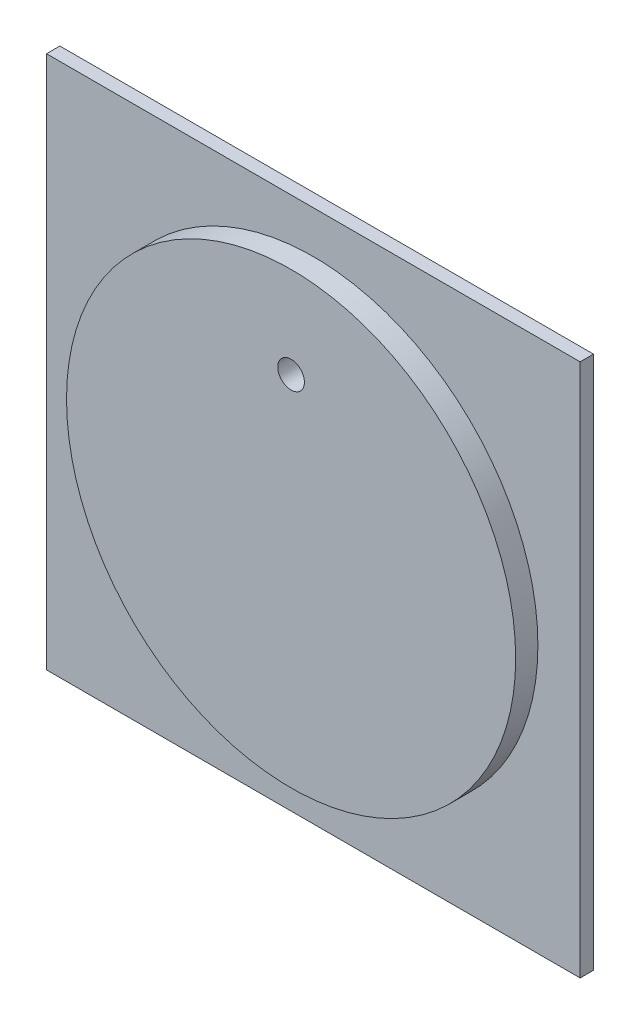
SolidWorks part; units mm, degrees
ref_plane "Front Plane" through (0, 0, 0) normal (0, 0, 1) x (1, 0, 0)
ref_plane "Top Plane" through (0, 0, 0) normal (0, 1, 0) x (1, 0, 0)
ref_plane "Right Plane" through (0, 0, 0) normal (1, 0, 0) x (0, 0, -1)
sketch "Sketch1" plane through (0, 0, 0) normal (0, 0, 1) x (1, 0, 0)
  line L1 (-30, -30) -> (30, -30)
  line L2 (-30, -30) -> (-30, 30)
  line L3 (-30, 30) -> (30, 30)
  line L4 (30, -30) -> (30, 30)
  line L5 (-30, -30) -> (30, 30) construction
  line L6 (-30, 30) -> (30, -30) construction
  line L7 (-30, -30) -> (30, -30)
  line L8 (-30, -30) -> (-30, -47)
  line L9 (-30, -47) -> (30, -47)
  line L10 (30, -30) -> (30, -47)
  circle A0 centre (0, 0) radius 25.25
  dimension "D1" = 50.5
  dimension "D2" = 60
  dimension "D3" = 60
  dimension "D4" = 47
extrude "Boss-Extrude1" add sketch "Sketch1" along normal blind 4 contours A0
extrude "Boss-Extrude2" add sketch "Sketch1<4>" along normal blind 1.5 contours L9 L2 | L1 L4 L3 L2 A0 region at (-29.1515, 0, 0)
sketch "Sketch1<4>" plane through (0, 0, 0) normal (0, 0, 1) x (1, 0, 0) same geometry as "Sketch1"
sketch "Sketch2" plane through (0, 0, 4) normal (0, 0, 1) x (1, 0, 0)
  circle A0 centre (0, 15) radius 1.5
  dimension "D1" = 3
  dimension "D2" = 15
extrude "Cut-Extrude1" cut sketch "Sketch2" against normal through all
